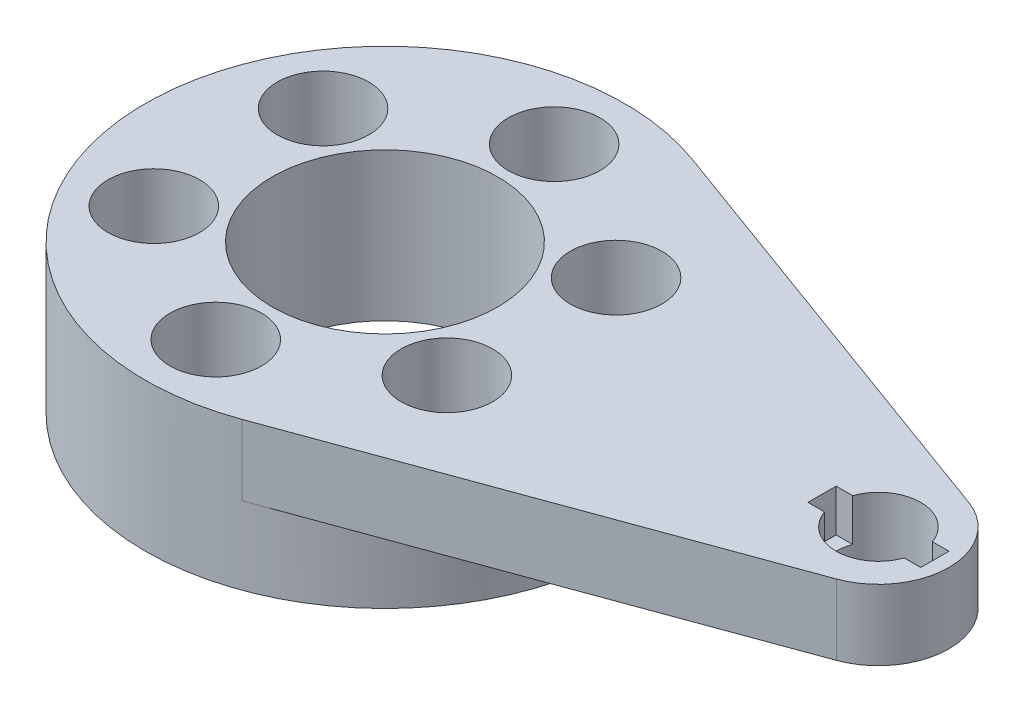
SolidWorks part; units mm, degrees
material "6061 합금"
ref_plane "정면" through (0, 0, 0) normal (0, 0, 1) x (1, 0, 0)
ref_plane "윗면" through (0, 0, 0) normal (0, 1, 0) x (1, 0, 0)
ref_plane "우측면" through (0, 0, 0) normal (1, 0, 0) x (0, 0, -1)
sketch "스케치1" plane through (0, 0, 0) normal (0, 1, 0) x (1, 0, 0)
  line L0 (0, 12) -> (0, 0) construction
  line L1 (0, 0) -> (10.3923, 6) construction
  line L2 (0, 0) -> (35, 0) construction
  line L3 (5.8286, 15.9696) -> (36.7143, 4.6969)
  line L4 (5.8286, -15.9696) -> (36.7143, -4.6969)
  circle A0 centre (0, 0) radius 17
  circle A2 centre (0, 0) radius 12
  circle A3 centre (0, 12) radius 2
  circle A4 centre (10.3923, 6) radius 2
  circle A5 centre (10.3923, -6) radius 2
  circle A6 centre (0, -12) radius 2
  circle A7 centre (-10.3923, -6) radius 2
  circle A8 centre (-10.3923, 6) radius 2
  circle A10 centre (35, 0) radius 3
  circle A11 centre (35, 0) radius 5
  circle A13 centre (0, 0) radius 8
  point P19 (0, 0)
  dimension "D1" = 24
  dimension "D2" = 6
  dimension "D3" = 4
  dimension "D5" = 34
  dimension "D7" = 6
  dimension "D8" = 10
  dimension "D9" = 16
  dimension "D4" = 60
  dimension "D6" = 35
extrude "보스-돌출1" add sketch "스케치1" along normal blind 5.5 contours A0 A8 A2 A3 A4 A5 A6 A7 | A8 A2 A7 A6 A5 A4 A3 region at (13.5359, 0, -9.469) region at (11.4779, 0, 2.0693)
extrude "보스-돌출2" add sketch "스케치1<3>" along normal blind 5 from surface contours A0 A8 A2 A3 A4 A5 A6 A7 | A8 A2 A7 A6 A5 A4 A3 | A11 L3 A0 L4 | A11 A10 region at (22.2546, 0, 0) region at (13.5359, 0, -9.469) region at (38.9812, 0, -2.785) region at (11.4779, 0, 2.0693) starting at face at (-10.3923, 5.5, -4)
sketch "스케치1<3>" plane through (0, 0, 0) normal (0, 1, 0) x (1, 0, 0) same geometry as "스케치1"
sketch "스케치2" plane through (0, 10.5, 0) normal (0, 1, 0) x (1, 0, 0)
  line L0 (0, 12) -> (0, 0) construction
  line L1 (0, 0) -> (10.3923, 6) construction
  circle A0 centre (0, 12) radius 3.25
  circle A1 centre (10.3923, 6) radius 3.25
  circle A2 centre (10.3923, -6) radius 3.25
  circle A3 centre (0, -12) radius 3.25
  circle A4 centre (-10.3923, -6) radius 3.25
  circle A5 centre (-10.3923, 6) radius 3.25
  point P15 (0, 0)
  dimension "D1" = 6.5
  dimension "D2" = 60
extrude "컷-돌출4" cut sketch "스케치2" against normal blind 6
sketch "스케치3" plane through (0, 10.5, 0) normal (0, 1, 0) x (1, 0, 0)
  line L1 (31, -1) -> (39, -1)
  line L2 (31, -1) -> (31, 1)
  line L3 (31, 1) -> (39, 1)
  line L4 (39, -1) -> (39, 1)
  line L5 (31, -1) -> (39, 1) construction
  line L6 (31, 1) -> (39, -1) construction
  point P0 (35, 0)
  dimension "D1" = 8
  dimension "D2" = 2
extrude "컷-돌출5" cut sketch "스케치3" against normal blind 3
